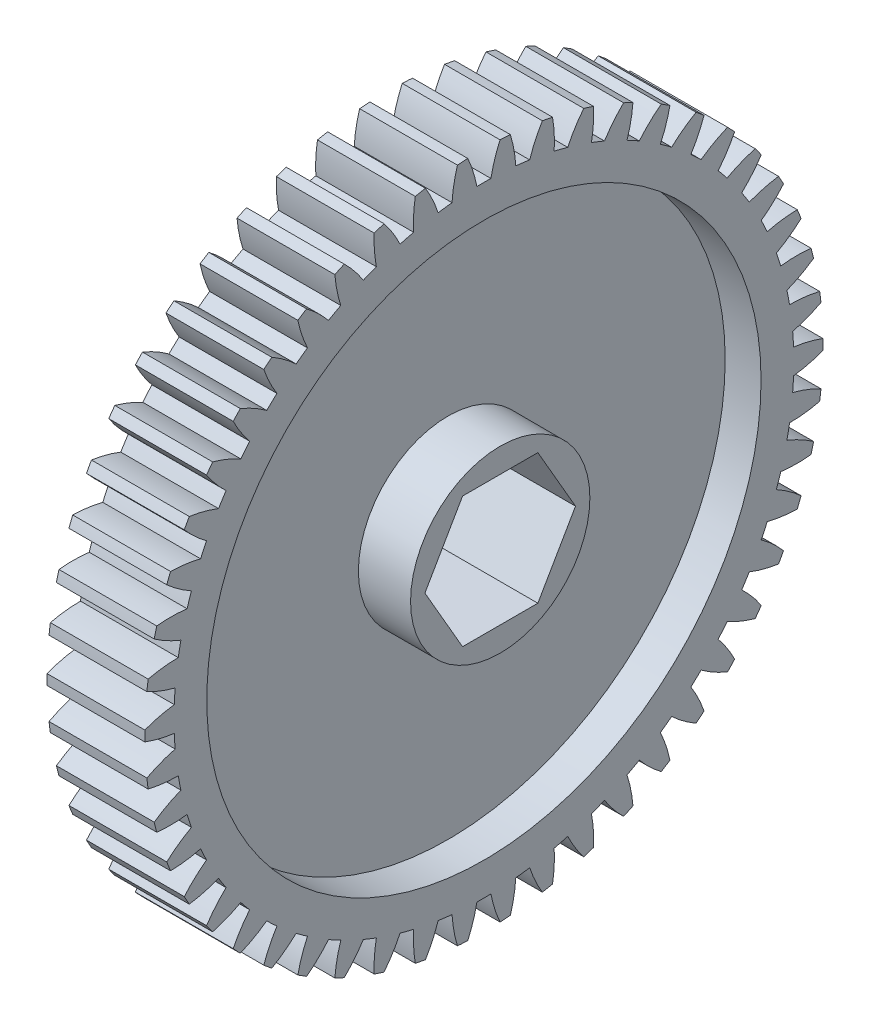
SolidWorks part; units mm, degrees
ref_plane "Front Plane" through (0, 0, 0) normal (0, 0, 1) x (1, 0, 0)
ref_plane "Top Plane" through (0, 0, 0) normal (0, 1, 0) x (1, 0, 0)
ref_plane "Right Plane" through (0, 0, 0) normal (1, 0, 0) x (0, 0, -1)
ref_plane "Plane1" through (0, 0, 0) normal (0, 0, -1) x (-1, 0, 0)
sketch "Sketch1" plane through (0, 0, 0) normal (0, 0, -1) x (-1, 0, 0)
  line L0 (-9.525, 33.02) -> (-9.525, 0)
  line L1 (-9.525, 0) -> (0, 0)
  line L2 (0, 0) -> (0, 33.02)
  line L3 (0, 33.02) -> (-9.525, 33.02)
  line L4 (-9.525, 0) -> (0, 0) construction
revolve "Revolve1" add sketch "Sketch1" angle 360 about L4 reverse direction yes
sketch "Sketch2" plane through (0, 0, 0) normal (-1, 0, 0) x (0, 0, 1)
  arc A0 (-2.5759, 32.9194) -> (-5.6917, 32.5258) centre (0, 0) ccw
  arc A1 (-5.6917, 32.5258) -> (-4.458, 29.8441) centre (-16.5343, 25.913) cw
  arc A2 (-4.458, 29.8441) -> (-3.104, 30.0151) centre (0, 0) cw
  arc A3 (-3.104, 30.0151) -> (-2.5759, 32.9194) centre (9.5705, 29.2108) cw
extrude "Cut-Extrude1" cut sketch "Sketch2" against normal through all
sketch "Sketch3" plane through (0, 0, 0) normal (-1, 0, 0) x (0, 0, 1)
  arc A0 (1.5703, 32.9826) -> (-1.5703, 32.9826) centre (0, 0) ccw
  arc A1 (-1.5703, 32.9826) -> (-0.6824, 30.1675) centre (-13.1561, 27.781) cw
  arc A2 (-0.6824, 30.1675) -> (0.6824, 30.1675) centre (0, 0) cw
  arc A3 (0.6824, 30.1675) -> (1.5703, 32.9826) centre (13.1561, 27.781) cw
extrude "Cut-Extrude2" cut sketch "Sketch3" against normal through all
sketch "Sketch4" plane through (0, 0, 0) normal (-1, 0, 0) x (0, 0, 1)
  arc A0 (5.6917, 32.5258) -> (2.5759, 32.9194) centre (0, 0) ccw
  arc A1 (2.5759, 32.9194) -> (3.104, 30.0151) centre (-9.5705, 29.2108) cw
  arc A2 (3.104, 30.0151) -> (4.458, 29.8441) centre (0, 0) cw
  arc A3 (4.458, 29.8441) -> (5.6917, 32.5258) centre (16.5343, 25.913) cw
extrude "Cut-Extrude3" cut sketch "Sketch4" against normal through all
sketch "Sketch5" plane through (0, 0, 0) normal (-1, 0, 0) x (0, 0, 1)
  arc A0 (9.7234, 31.5559) -> (6.6815, 32.3369) centre (0, 0) ccw
  arc A1 (6.6815, 32.3369) -> (6.8414, 29.3894) centre (-5.834, 30.18) cw
  arc A2 (6.8414, 29.3894) -> (8.1633, 29.05) centre (0, 0) cw
  arc A3 (8.1633, 29.05) -> (9.7234, 31.5559) centre (19.6517, 23.6364) cw
extrude "Cut-Extrude4" cut sketch "Sketch5" against normal through all
sketch "Sketch6" plane through (0, 0, 0) normal (-1, 0, 0) x (0, 0, 1)
  arc A0 (13.6017, 30.0884) -> (10.6817, 31.2445) centre (0, 0) ccw
  arc A1 (10.6817, 31.2445) -> (10.4709, 28.3002) centre (-2.0054, 30.6732) cw
  arc A2 (10.4709, 28.3002) -> (11.7399, 27.7978) centre (0, 0) cw
  arc A3 (11.7399, 27.7978) -> (13.6017, 30.0884) centre (22.4591, 20.987) cw
extrude "Cut-Extrude5" cut sketch "Sketch6" against normal through all
sketch "Sketch7" plane through (0, 0, 0) normal (-1, 0, 0) x (0, 0, 1)
  arc A0 (17.2655, 28.1464) -> (14.5135, 29.6594) centre (0, 0) ccw
  arc A1 (14.5135, 29.6594) -> (13.9353, 26.7647) centre (1.8548, 30.6827) cw
  arc A2 (13.9353, 26.7647) -> (15.1313, 26.1072) centre (0, 0) cw
  arc A3 (15.1313, 26.1072) -> (17.2655, 28.1464) centre (24.9124, 18.0066) cw
extrude "Cut-Extrude6" cut sketch "Sketch7" against normal through all
sketch "Sketch8" plane through (0, 0, 0) normal (-1, 0, 0) x (0, 0, 1)
  arc A0 (20.6571, 25.7605) -> (18.1163, 27.6065) centre (0, 0) ccw
  arc A1 (18.1163, 27.6065) -> (17.1799, 24.8071) centre (5.6857, 30.2083) cw
  arc A2 (17.1799, 24.8071) -> (18.2841, 24.0049) centre (0, 0) cw
  arc A3 (18.2841, 24.0049) -> (20.6571, 25.7605) centre (26.9728, 14.7423) cw
extrude "Cut-Extrude7" cut sketch "Sketch8" against normal through all
sketch "Sketch9" plane through (0, 0, 0) normal (-1, 0, 0) x (0, 0, 1)
  arc A0 (23.7228, 22.9684) -> (21.4335, 25.1182) centre (0, 0) ccw
  arc A1 (21.4335, 25.1182) -> (20.1536, 22.4583) centre (9.427, 29.2575) cw
  arc A2 (20.1536, 22.4583) -> (21.1485, 21.524) centre (0, 0) cw
  arc A3 (21.1485, 21.524) -> (23.7228, 22.9684) centre (28.6078, 11.2455) cw
extrude "Cut-Extrude8" cut sketch "Sketch9" against normal through all
sketch "Sketch10" plane through (0, 0, 0) normal (-1, 0, 0) x (0, 0, 1)
  arc A0 (26.4145, 19.814) -> (24.4126, 22.2338) centre (0, 0) ccw
  arc A1 (24.4126, 22.2338) -> (22.8095, 19.7553) centre (13.0196, 27.8452) cw
  arc A2 (22.8095, 19.7553) -> (23.6794, 18.7037) centre (0, 0) cw
  arc A3 (23.6794, 18.7037) -> (26.4145, 19.814) centre (29.7917, 7.5713) cw
extrude "Cut-Extrude9" cut sketch "Sketch10" against normal through all
sketch "Sketch11" plane through (0, 0, 0) normal (-1, 0, 0) x (0, 0, 1)
  arc A0 (28.6896, 16.3472) -> (27.0068, 18.9988) centre (0, 0) ccw
  arc A1 (27.0068, 18.9988) -> (25.1056, 16.7407) centre (16.4068, 25.9939) cw
  arc A2 (25.1056, 16.7407) -> (25.8369, 15.5884) centre (0, 0) cw
  arc A3 (25.8369, 15.5884) -> (28.6896, 16.3472) centre (30.5057, 3.7777) cw
extrude "Cut-Extrude10" cut sketch "Sketch11" against normal through all
sketch "Sketch12" plane through (0, 0, 0) normal (-1, 0, 0) x (0, 0, 1)
  arc A0 (30.5122, 12.6225) -> (29.175, 15.4641) centre (0, 0) ccw
  arc A1 (29.175, 15.4641) -> (27.0058, 13.4621) centre (19.5354, 23.7326) cw
  arc A2 (27.0058, 13.4621) -> (27.5869, 12.2272) centre (0, 0) cw
  arc A3 (27.5869, 12.2272) -> (30.5122, 12.6225) centre (30.7386, -0.0755) cw
extrude "Cut-Extrude11" cut sketch "Sketch12" against normal through all
sketch "Sketch13" plane through (0, 0, 0) normal (-1, 0, 0) x (0, 0, 1)
  arc A0 (31.8536, 8.6988) -> (30.8831, 11.6856) centre (0, 0) ccw
  arc A1 (30.8831, 11.6856) -> (28.4801, 9.9713) centre (22.3558, 21.097) cw
  arc A2 (28.4801, 9.9713) -> (28.9019, 8.6733) centre (0, 0) cw
  arc A3 (28.9019, 8.6733) -> (31.8536, 8.6988) centre (30.4868, -3.9274) cw
extrude "Cut-Extrude12" cut sketch "Sketch13" against normal through all
sketch "Sketch14" plane through (0, 0, 0) normal (-1, 0, 0) x (0, 0, 1)
  arc A0 (32.6927, 4.6379) -> (32.1042, 7.7228) centre (0, 0) ccw
  arc A1 (32.1042, 7.7228) -> (29.5053, 6.3231) centre (24.8237, 18.1288) cw
  arc A2 (29.5053, 6.3231) -> (29.761, 4.9825) centre (0, 0) cw
  arc A3 (29.761, 4.9825) -> (32.6927, 4.6379) centre (29.7541, -7.7175) cw
extrude "Cut-Extrude13" cut sketch "Sketch14" against normal through all
sketch "Sketch15" plane through (0, 0, 0) normal (-1, 0, 0) x (0, 0, 1)
  arc A0 (33.0162, 0.5038) -> (32.819, 3.6382) centre (0, 0) ccw
  arc A1 (32.819, 3.6382) -> (30.0651, 2.5753) centre (26.9001, 14.8746) cw
  arc A2 (30.0651, 2.5753) -> (30.1508, 1.2132) centre (0, 0) cw
  arc A3 (30.1508, 1.2132) -> (33.0162, 0.5038) centre (28.5522, -11.3858) cw
extrude "Cut-Extrude14" cut sketch "Sketch15" against normal through all
sketch "Sketch16" plane through (0, 0, 0) normal (-1, 0, 0) x (0, 0, 1)
  arc A0 (32.819, -3.6382) -> (33.0162, -0.5038) centre (0, 0) ccw
  arc A1 (33.0162, -0.5038) -> (30.1508, -1.2132) centre (28.5522, 11.3858) cw
  arc A2 (30.1508, -1.2132) -> (30.0651, -2.5753) centre (0, 0) cw
  arc A3 (30.0651, -2.5753) -> (32.819, -3.6382) centre (26.9001, -14.8746) cw
extrude "Cut-Extrude15" cut sketch "Sketch16" against normal through all
sketch "Sketch17" plane through (0, 0, 0) normal (-1, 0, 0) x (0, 0, 1)
  arc A0 (32.1042, -7.7228) -> (32.6927, -4.6379) centre (0, 0) ccw
  arc A1 (32.6927, -4.6379) -> (29.761, -4.9825) centre (29.7541, 7.7175) cw
  arc A2 (29.761, -4.9825) -> (29.5053, -6.3231) centre (0, 0) cw
  arc A3 (29.5053, -6.3231) -> (32.1042, -7.7228) centre (24.8237, -18.1288) cw
extrude "Cut-Extrude16" cut sketch "Sketch17" against normal through all
sketch "Sketch18" plane through (0, 0, 0) normal (-1, 0, 0) x (0, 0, 1)
  arc A0 (30.8831, -11.6856) -> (31.8536, -8.6988) centre (0, 0) ccw
  arc A1 (31.8536, -8.6988) -> (28.9019, -8.6733) centre (30.4868, 3.9274) cw
  arc A2 (28.9019, -8.6733) -> (28.4801, -9.9713) centre (0, 0) cw
  arc A3 (28.4801, -9.9713) -> (30.8831, -11.6856) centre (22.3558, -21.097) cw
extrude "Cut-Extrude17" cut sketch "Sketch18" against normal through all
sketch "Sketch19" plane through (0, 0, 0) normal (-1, 0, 0) x (0, 0, 1)
  arc A0 (29.175, -15.4641) -> (30.5122, -12.6225) centre (0, 0) ccw
  arc A1 (30.5122, -12.6225) -> (27.5869, -12.2272) centre (30.7386, 0.0755) cw
  arc A2 (27.5869, -12.2272) -> (27.0058, -13.4621) centre (0, 0) cw
  arc A3 (27.0058, -13.4621) -> (29.175, -15.4641) centre (19.5354, -23.7326) cw
extrude "Cut-Extrude18" cut sketch "Sketch19" against normal through all
sketch "Sketch20" plane through (0, 0, 0) normal (-1, 0, 0) x (0, 0, 1)
  arc A0 (27.0068, -18.9988) -> (28.6896, -16.3472) centre (0, 0) ccw
  arc A1 (28.6896, -16.3472) -> (25.8369, -15.5884) centre (30.5057, -3.7777) cw
  arc A2 (25.8369, -15.5884) -> (25.1056, -16.7407) centre (0, 0) cw
  arc A3 (25.1056, -16.7407) -> (27.0068, -18.9988) centre (16.4068, -25.9939) cw
extrude "Cut-Extrude19" cut sketch "Sketch20" against normal through all
sketch "Sketch21" plane through (0, 0, 0) normal (-1, 0, 0) x (0, 0, 1)
  arc A0 (24.4126, -22.2338) -> (26.4145, -19.814) centre (0, 0) ccw
  arc A1 (26.4145, -19.814) -> (23.6794, -18.7037) centre (29.7917, -7.5713) cw
  arc A2 (23.6794, -18.7037) -> (22.8095, -19.7553) centre (0, 0) cw
  arc A3 (22.8095, -19.7553) -> (24.4126, -22.2338) centre (13.0196, -27.8452) cw
extrude "Cut-Extrude20" cut sketch "Sketch21" against normal through all
sketch "Sketch22" plane through (0, 0, 0) normal (-1, 0, 0) x (0, 0, 1)
  arc A0 (21.4335, -25.1182) -> (23.7228, -22.9684) centre (0, 0) ccw
  arc A1 (23.7228, -22.9684) -> (21.1485, -21.524) centre (28.6078, -11.2455) cw
  arc A2 (21.1485, -21.524) -> (20.1536, -22.4583) centre (0, 0) cw
  arc A3 (20.1536, -22.4583) -> (21.4335, -25.1182) centre (9.427, -29.2575) cw
extrude "Cut-Extrude21" cut sketch "Sketch22" against normal through all
sketch "Sketch23" plane through (0, 0, 0) normal (-1, 0, 0) x (0, 0, 1)
  arc A0 (18.1163, -27.6065) -> (20.6571, -25.7605) centre (0, 0) ccw
  arc A1 (20.6571, -25.7605) -> (18.2841, -24.0049) centre (26.9728, -14.7423) cw
  arc A2 (18.2841, -24.0049) -> (17.1799, -24.8071) centre (0, 0) cw
  arc A3 (17.1799, -24.8071) -> (18.1163, -27.6065) centre (5.6857, -30.2083) cw
extrude "Cut-Extrude22" cut sketch "Sketch23" against normal through all
sketch "Sketch24" plane through (0, 0, 0) normal (-1, 0, 0) x (0, 0, 1)
  arc A0 (14.5135, -29.6594) -> (17.2655, -28.1464) centre (0, 0) ccw
  arc A1 (17.2655, -28.1464) -> (15.1313, -26.1072) centre (24.9124, -18.0066) cw
  arc A2 (15.1313, -26.1072) -> (13.9353, -26.7647) centre (0, 0) cw
  arc A3 (13.9353, -26.7647) -> (14.5135, -29.6594) centre (1.8548, -30.6827) cw
extrude "Cut-Extrude23" cut sketch "Sketch24" against normal through all
sketch "Sketch25" plane through (0, 0, 0) normal (-1, 0, 0) x (0, 0, 1)
  arc A0 (10.6817, -31.2445) -> (13.6017, -30.0884) centre (0, 0) ccw
  arc A1 (13.6017, -30.0884) -> (11.7399, -27.7978) centre (22.4591, -20.987) cw
  arc A2 (11.7399, -27.7978) -> (10.4709, -28.3002) centre (0, 0) cw
  arc A3 (10.4709, -28.3002) -> (10.6817, -31.2445) centre (-2.0054, -30.6732) cw
extrude "Cut-Extrude24" cut sketch "Sketch25" against normal through all
sketch "Sketch26" plane through (0, 0, 0) normal (-1, 0, 0) x (0, 0, 1)
  arc A0 (6.6815, -32.3369) -> (9.7234, -31.5559) centre (0, 0) ccw
  arc A1 (9.7234, -31.5559) -> (8.1633, -29.05) centre (19.6517, -23.6364) cw
  arc A2 (8.1633, -29.05) -> (6.8414, -29.3894) centre (0, 0) cw
  arc A3 (6.8414, -29.3894) -> (6.6815, -32.3369) centre (-5.834, -30.18) cw
extrude "Cut-Extrude25" cut sketch "Sketch26" against normal through all
sketch "Sketch27" plane through (0, 0, 0) normal (-1, 0, 0) x (0, 0, 1)
  arc A0 (2.5759, -32.9194) -> (5.6917, -32.5258) centre (0, 0) ccw
  arc A1 (5.6917, -32.5258) -> (4.458, -29.8441) centre (16.5343, -25.913) cw
  arc A2 (4.458, -29.8441) -> (3.104, -30.0151) centre (0, 0) cw
  arc A3 (3.104, -30.0151) -> (2.5759, -32.9194) centre (-9.5705, -29.2108) cw
extrude "Cut-Extrude26" cut sketch "Sketch27" against normal through all
sketch "Sketch28" plane through (0, 0, 0) normal (-1, 0, 0) x (0, 0, 1)
  arc A0 (-1.5703, -32.9826) -> (1.5703, -32.9826) centre (0, 0) ccw
  arc A1 (1.5703, -32.9826) -> (0.6824, -30.1675) centre (13.1561, -27.781) cw
  arc A2 (0.6824, -30.1675) -> (-0.6824, -30.1675) centre (0, 0) cw
  arc A3 (-0.6824, -30.1675) -> (-1.5703, -32.9826) centre (-13.1561, -27.781) cw
extrude "Cut-Extrude27" cut sketch "Sketch28" against normal through all
sketch "Sketch29" plane through (0, 0, 0) normal (-1, 0, 0) x (0, 0, 1)
  arc A0 (-5.6917, -32.5258) -> (-2.5759, -32.9194) centre (0, 0) ccw
  arc A1 (-2.5759, -32.9194) -> (-3.104, -30.0151) centre (9.5705, -29.2108) cw
  arc A2 (-3.104, -30.0151) -> (-4.458, -29.8441) centre (0, 0) cw
  arc A3 (-4.458, -29.8441) -> (-5.6917, -32.5258) centre (-16.5343, -25.913) cw
extrude "Cut-Extrude28" cut sketch "Sketch29" against normal through all
sketch "Sketch30" plane through (0, 0, 0) normal (-1, 0, 0) x (0, 0, 1)
  arc A0 (-9.7234, -31.5559) -> (-6.6815, -32.3369) centre (0, 0) ccw
  arc A1 (-6.6815, -32.3369) -> (-6.8414, -29.3894) centre (5.834, -30.18) cw
  arc A2 (-6.8414, -29.3894) -> (-8.1633, -29.05) centre (0, 0) cw
  arc A3 (-8.1633, -29.05) -> (-9.7234, -31.5559) centre (-19.6517, -23.6364) cw
extrude "Cut-Extrude29" cut sketch "Sketch30" against normal through all
sketch "Sketch31" plane through (0, 0, 0) normal (-1, 0, 0) x (0, 0, 1)
  arc A0 (-13.6017, -30.0884) -> (-10.6817, -31.2445) centre (0, 0) ccw
  arc A1 (-10.6817, -31.2445) -> (-10.4709, -28.3002) centre (2.0054, -30.6732) cw
  arc A2 (-10.4709, -28.3002) -> (-11.7399, -27.7978) centre (0, 0) cw
  arc A3 (-11.7399, -27.7978) -> (-13.6017, -30.0884) centre (-22.4591, -20.987) cw
extrude "Cut-Extrude30" cut sketch "Sketch31" against normal through all
sketch "Sketch32" plane through (0, 0, 0) normal (-1, 0, 0) x (0, 0, 1)
  arc A0 (-17.2655, -28.1464) -> (-14.5135, -29.6594) centre (0, 0) ccw
  arc A1 (-14.5135, -29.6594) -> (-13.9353, -26.7647) centre (-1.8548, -30.6827) cw
  arc A2 (-13.9353, -26.7647) -> (-15.1313, -26.1072) centre (0, 0) cw
  arc A3 (-15.1313, -26.1072) -> (-17.2655, -28.1464) centre (-24.9124, -18.0066) cw
extrude "Cut-Extrude31" cut sketch "Sketch32" against normal through all
sketch "Sketch33" plane through (0, 0, 0) normal (-1, 0, 0) x (0, 0, 1)
  arc A0 (-20.6571, -25.7605) -> (-18.1163, -27.6065) centre (0, 0) ccw
  arc A1 (-18.1163, -27.6065) -> (-17.1799, -24.8071) centre (-5.6857, -30.2083) cw
  arc A2 (-17.1799, -24.8071) -> (-18.2841, -24.0049) centre (0, 0) cw
  arc A3 (-18.2841, -24.0049) -> (-20.6571, -25.7605) centre (-26.9728, -14.7423) cw
extrude "Cut-Extrude32" cut sketch "Sketch33" against normal through all
sketch "Sketch34" plane through (0, 0, 0) normal (-1, 0, 0) x (0, 0, 1)
  arc A0 (-23.7228, -22.9684) -> (-21.4335, -25.1182) centre (0, 0) ccw
  arc A1 (-21.4335, -25.1182) -> (-20.1536, -22.4583) centre (-9.427, -29.2575) cw
  arc A2 (-20.1536, -22.4583) -> (-21.1485, -21.524) centre (0, 0) cw
  arc A3 (-21.1485, -21.524) -> (-23.7228, -22.9684) centre (-28.6078, -11.2455) cw
extrude "Cut-Extrude33" cut sketch "Sketch34" against normal through all
sketch "Sketch35" plane through (0, 0, 0) normal (-1, 0, 0) x (0, 0, 1)
  arc A0 (-26.4145, -19.814) -> (-24.4126, -22.2338) centre (0, 0) ccw
  arc A1 (-24.4126, -22.2338) -> (-22.8095, -19.7553) centre (-13.0196, -27.8452) cw
  arc A2 (-22.8095, -19.7553) -> (-23.6794, -18.7037) centre (0, 0) cw
  arc A3 (-23.6794, -18.7037) -> (-26.4145, -19.814) centre (-29.7917, -7.5713) cw
extrude "Cut-Extrude34" cut sketch "Sketch35" against normal through all
sketch "Sketch36" plane through (0, 0, 0) normal (-1, 0, 0) x (0, 0, 1)
  arc A0 (-28.6896, -16.3472) -> (-27.0068, -18.9988) centre (0, 0) ccw
  arc A1 (-27.0068, -18.9988) -> (-25.1056, -16.7407) centre (-16.4068, -25.9939) cw
  arc A2 (-25.1056, -16.7407) -> (-25.8369, -15.5884) centre (0, 0) cw
  arc A3 (-25.8369, -15.5884) -> (-28.6896, -16.3472) centre (-30.5057, -3.7777) cw
extrude "Cut-Extrude35" cut sketch "Sketch36" against normal through all
sketch "Sketch37" plane through (0, 0, 0) normal (-1, 0, 0) x (0, 0, 1)
  arc A0 (-30.5122, -12.6225) -> (-29.175, -15.4641) centre (0, 0) ccw
  arc A1 (-29.175, -15.4641) -> (-27.0058, -13.4621) centre (-19.5354, -23.7326) cw
  arc A2 (-27.0058, -13.4621) -> (-27.5869, -12.2272) centre (0, 0) cw
  arc A3 (-27.5869, -12.2272) -> (-30.5122, -12.6225) centre (-30.7386, 0.0755) cw
extrude "Cut-Extrude36" cut sketch "Sketch37" against normal through all
sketch "Sketch38" plane through (0, 0, 0) normal (-1, 0, 0) x (0, 0, 1)
  arc A0 (-31.8536, -8.6988) -> (-30.8831, -11.6856) centre (0, 0) ccw
  arc A1 (-30.8831, -11.6856) -> (-28.4801, -9.9713) centre (-22.3558, -21.097) cw
  arc A2 (-28.4801, -9.9713) -> (-28.9019, -8.6733) centre (0, 0) cw
  arc A3 (-28.9019, -8.6733) -> (-31.8536, -8.6988) centre (-30.4868, 3.9274) cw
extrude "Cut-Extrude37" cut sketch "Sketch38" against normal through all
sketch "Sketch39" plane through (0, 0, 0) normal (-1, 0, 0) x (0, 0, 1)
  arc A0 (-32.6927, -4.6379) -> (-32.1042, -7.7228) centre (0, 0) ccw
  arc A1 (-32.1042, -7.7228) -> (-29.5053, -6.3231) centre (-24.8237, -18.1288) cw
  arc A2 (-29.5053, -6.3231) -> (-29.761, -4.9825) centre (0, 0) cw
  arc A3 (-29.761, -4.9825) -> (-32.6927, -4.6379) centre (-29.7541, 7.7175) cw
extrude "Cut-Extrude38" cut sketch "Sketch39" against normal through all
sketch "Sketch40" plane through (0, 0, 0) normal (-1, 0, 0) x (0, 0, 1)
  arc A0 (-33.0162, -0.5038) -> (-32.819, -3.6382) centre (0, 0) ccw
  arc A1 (-32.819, -3.6382) -> (-30.0651, -2.5753) centre (-26.9001, -14.8746) cw
  arc A2 (-30.0651, -2.5753) -> (-30.1508, -1.2132) centre (0, 0) cw
  arc A3 (-30.1508, -1.2132) -> (-33.0162, -0.5038) centre (-28.5522, 11.3858) cw
extrude "Cut-Extrude39" cut sketch "Sketch40" against normal through all
sketch "Sketch41" plane through (0, 0, 0) normal (-1, 0, 0) x (0, 0, 1)
  arc A0 (-32.819, 3.6382) -> (-33.0162, 0.5038) centre (0, 0) ccw
  arc A1 (-33.0162, 0.5038) -> (-30.1508, 1.2132) centre (-28.5522, -11.3858) cw
  arc A2 (-30.1508, 1.2132) -> (-30.0651, 2.5753) centre (0, 0) cw
  arc A3 (-30.0651, 2.5753) -> (-32.819, 3.6382) centre (-26.9001, 14.8746) cw
extrude "Cut-Extrude40" cut sketch "Sketch41" against normal through all
sketch "Sketch42" plane through (0, 0, 0) normal (-1, 0, 0) x (0, 0, 1)
  arc A0 (-32.1042, 7.7228) -> (-32.6927, 4.6379) centre (0, 0) ccw
  arc A1 (-32.6927, 4.6379) -> (-29.761, 4.9825) centre (-29.7541, -7.7175) cw
  arc A2 (-29.761, 4.9825) -> (-29.5053, 6.3231) centre (0, 0) cw
  arc A3 (-29.5053, 6.3231) -> (-32.1042, 7.7228) centre (-24.8237, 18.1288) cw
extrude "Cut-Extrude41" cut sketch "Sketch42" against normal through all
sketch "Sketch43" plane through (0, 0, 0) normal (-1, 0, 0) x (0, 0, 1)
  arc A0 (-30.8831, 11.6856) -> (-31.8536, 8.6988) centre (0, 0) ccw
  arc A1 (-31.8536, 8.6988) -> (-28.9019, 8.6733) centre (-30.4868, -3.9274) cw
  arc A2 (-28.9019, 8.6733) -> (-28.4801, 9.9713) centre (0, 0) cw
  arc A3 (-28.4801, 9.9713) -> (-30.8831, 11.6856) centre (-22.3558, 21.097) cw
extrude "Cut-Extrude42" cut sketch "Sketch43" against normal through all
sketch "Sketch44" plane through (0, 0, 0) normal (-1, 0, 0) x (0, 0, 1)
  arc A0 (-29.175, 15.4641) -> (-30.5122, 12.6225) centre (0, 0) ccw
  arc A1 (-30.5122, 12.6225) -> (-27.5869, 12.2272) centre (-30.7386, -0.0755) cw
  arc A2 (-27.5869, 12.2272) -> (-27.0058, 13.4621) centre (0, 0) cw
  arc A3 (-27.0058, 13.4621) -> (-29.175, 15.4641) centre (-19.5354, 23.7326) cw
extrude "Cut-Extrude43" cut sketch "Sketch44" against normal through all
sketch "Sketch45" plane through (0, 0, 0) normal (-1, 0, 0) x (0, 0, 1)
  arc A0 (-27.0068, 18.9988) -> (-28.6896, 16.3472) centre (0, 0) ccw
  arc A1 (-28.6896, 16.3472) -> (-25.8369, 15.5884) centre (-30.5057, 3.7777) cw
  arc A2 (-25.8369, 15.5884) -> (-25.1056, 16.7407) centre (0, 0) cw
  arc A3 (-25.1056, 16.7407) -> (-27.0068, 18.9988) centre (-16.4068, 25.9939) cw
extrude "Cut-Extrude44" cut sketch "Sketch45" against normal through all
sketch "Sketch46" plane through (0, 0, 0) normal (-1, 0, 0) x (0, 0, 1)
  arc A0 (-24.4126, 22.2338) -> (-26.4145, 19.814) centre (0, 0) ccw
  arc A1 (-26.4145, 19.814) -> (-23.6794, 18.7037) centre (-29.7917, 7.5713) cw
  arc A2 (-23.6794, 18.7037) -> (-22.8095, 19.7553) centre (0, 0) cw
  arc A3 (-22.8095, 19.7553) -> (-24.4126, 22.2338) centre (-13.0196, 27.8452) cw
extrude "Cut-Extrude45" cut sketch "Sketch46" against normal through all
sketch "Sketch47" plane through (0, 0, 0) normal (-1, 0, 0) x (0, 0, 1)
  arc A0 (-21.4335, 25.1182) -> (-23.7228, 22.9684) centre (0, 0) ccw
  arc A1 (-23.7228, 22.9684) -> (-21.1485, 21.524) centre (-28.6078, 11.2455) cw
  arc A2 (-21.1485, 21.524) -> (-20.1536, 22.4583) centre (0, 0) cw
  arc A3 (-20.1536, 22.4583) -> (-21.4335, 25.1182) centre (-9.427, 29.2575) cw
extrude "Cut-Extrude46" cut sketch "Sketch47" against normal through all
sketch "Sketch48" plane through (0, 0, 0) normal (-1, 0, 0) x (0, 0, 1)
  arc A0 (-18.1163, 27.6065) -> (-20.6571, 25.7605) centre (0, 0) ccw
  arc A1 (-20.6571, 25.7605) -> (-18.2841, 24.0049) centre (-26.9728, 14.7423) cw
  arc A2 (-18.2841, 24.0049) -> (-17.1799, 24.8071) centre (0, 0) cw
  arc A3 (-17.1799, 24.8071) -> (-18.1163, 27.6065) centre (-5.6857, 30.2083) cw
extrude "Cut-Extrude47" cut sketch "Sketch48" against normal through all
sketch "Sketch49" plane through (0, 0, 0) normal (-1, 0, 0) x (0, 0, 1)
  arc A0 (-14.5135, 29.6594) -> (-17.2655, 28.1464) centre (0, 0) ccw
  arc A1 (-17.2655, 28.1464) -> (-15.1313, 26.1072) centre (-24.9124, 18.0066) cw
  arc A2 (-15.1313, 26.1072) -> (-13.9353, 26.7647) centre (0, 0) cw
  arc A3 (-13.9353, 26.7647) -> (-14.5135, 29.6594) centre (-1.8548, 30.6827) cw
extrude "Cut-Extrude48" cut sketch "Sketch49" against normal through all
sketch "Sketch50" plane through (0, 0, 0) normal (-1, 0, 0) x (0, 0, 1)
  arc A0 (-10.6817, 31.2445) -> (-13.6017, 30.0884) centre (0, 0) ccw
  arc A1 (-13.6017, 30.0884) -> (-11.7399, 27.7978) centre (-22.4591, 20.987) cw
  arc A2 (-11.7399, 27.7978) -> (-10.4709, 28.3002) centre (0, 0) cw
  arc A3 (-10.4709, 28.3002) -> (-10.6817, 31.2445) centre (2.0054, 30.6732) cw
extrude "Cut-Extrude49" cut sketch "Sketch50" against normal through all
sketch "Sketch51" plane through (0, 0, 0) normal (-1, 0, 0) x (0, 0, 1)
  arc A0 (-6.6815, 32.3369) -> (-9.7234, 31.5559) centre (0, 0) ccw
  arc A1 (-9.7234, 31.5559) -> (-8.1633, 29.05) centre (-19.6517, 23.6364) cw
  arc A2 (-8.1633, 29.05) -> (-6.8414, 29.3894) centre (0, 0) cw
  arc A3 (-6.8414, 29.3894) -> (-6.6815, 32.3369) centre (5.834, 30.18) cw
extrude "Cut-Extrude50" cut sketch "Sketch51" against normal through all
hole_wizard "Hole1" positions "Sketch53" profile "Sketch52" legacy
sketch "Sketch53" plane through (9.525, 0, 0) normal (1, 0, 0) x (0, 0, -1)
  point P0 (0, 0)
sketch "Sketch52" plane through (9.525, 0, 0) normal (0, 1, 0) x (0, 0, -1)
  line L0 (0, 0) -> (0, 3.4925)
  line L1 (0, 3.4925) -> (26.9875, 3.4925)
  line L2 (26.9875, 3.4925) -> (26.9875, 0)
  line L3 (26.9875, 0) -> (0, 0)
  line L4 (0, 110) -> (0, -10) construction
  dimension "Diameter" = 53.975
  dimension "Depth" = 3.4925
sketch "Sketch54" plane through (6.0325, 0, 0) normal (1, 0, 0) x (0, 0, -1)
  circle A0 centre (0, 0) radius 8.7312
extrude "Boss-Extrude1" add sketch "Sketch54" along normal blind 5.08
hole_wizard "Hole2" positions "Sketch56" profile "Sketch55" legacy
sketch "Sketch56" plane through (0, 0, 0) normal (-1, 0, 0) x (0, 0, 1)
  point P0 (0, 0)
sketch "Sketch55" plane through (0, 0, 0) normal (0, 1, 0) x (0, 0, 1)
  line L0 (0, 0) -> (0, 3.4925)
  line L1 (0, 3.4925) -> (26.9875, 3.4925)
  line L2 (26.9875, 3.4925) -> (26.9875, 0)
  line L3 (26.9875, 0) -> (0, 0)
  line L4 (0, 110) -> (0, -10) construction
  dimension "Diameter" = 53.975
  dimension "Depth" = 3.4925
sketch "Sketch57" plane through (3.4925, 0, 0) normal (-1, 0, 0) x (0, 0, 1)
  circle A0 centre (0, 0) radius 8.7312
extrude "Boss-Extrude2" add sketch "Sketch57" along normal blind 5.08
sketch "Sketch58" plane through (-1.5875, 0, 0) normal (-1, 0, 0) x (0, 0, 1)
  line L0 (-3.6662, -6.35) -> (3.6662, -6.35)
  line L1 (3.6662, -6.35) -> (7.3323, 0)
  line L2 (7.3323, 0) -> (3.6662, 6.35)
  line L3 (3.6662, 6.35) -> (-3.6662, 6.35)
  line L4 (-3.6662, 6.35) -> (-7.3323, 0)
  line L5 (-7.3323, 0) -> (-3.6662, -6.35)
extrude "Cut-Extrude51" cut sketch "Sketch58" against normal through all
